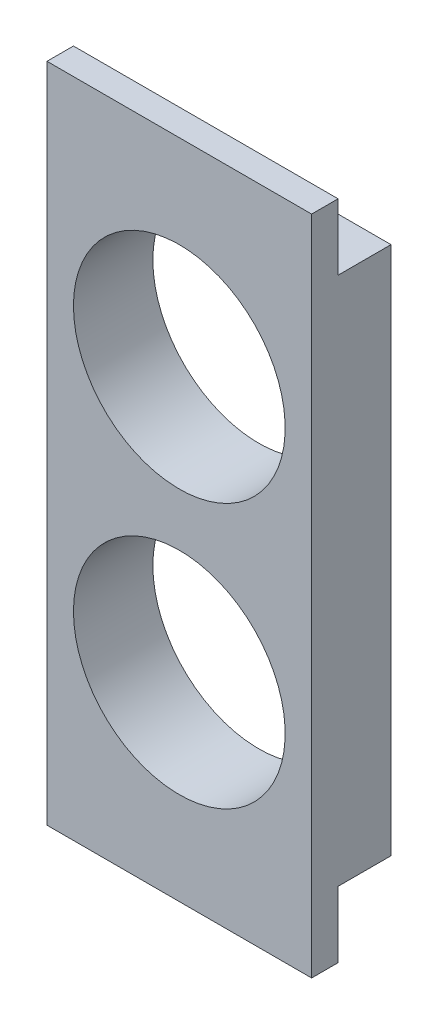
SolidWorks part; units mm, degrees
ref_plane "前视基准面" through (0, 0, 0) normal (0, 0, 1) x (1, 0, 0)
ref_plane "上视基准面" through (0, 0, 0) normal (0, 1, 0) x (1, 0, 0)
ref_plane "右视基准面" through (0, 0, 0) normal (1, 0, 0) x (0, 0, -1)
sketch "草图1" plane through (0, 0, 0) normal (0, 0, 1) x (1, 0, 0)
  line L0 (0, 100) -> (0, -100) construction
  line L1 (50, -100) -> (-50, -100)
  line L2 (50, -100) -> (50, 100)
  line L3 (50, 100) -> (-50, 100)
  line L4 (-50, -100) -> (-50, 100)
  line L5 (50, -100) -> (-50, 100) construction
  line L6 (50, 100) -> (-50, -100) construction
  line L7 (-50, 0) -> (50, 0) construction
  circle A0 centre (0, 50) radius 40
  circle A1 centre (0, -50) radius 40
  point P0 (0, 0)
  dimension "D3" = 80
  dimension "D1" = 100
  dimension "D2" = 200
  dimension "D4" = 50
extrude "凸台-拉伸1" add sketch "草图1" along normal blind 20
sketch "草图2" plane through (0, 0, 20) normal (0, 0, 1) x (1, 0, 0)
  line L0 (-50, 100) -> (-50, -100) construction
  line L1 (50, -125) -> (-50, -125)
  line L2 (50, -125) -> (50, 125)
  line L3 (50, 125) -> (-50, 125)
  line L4 (-50, -125) -> (-50, 125)
  line L5 (50, -125) -> (-50, 125) construction
  line L6 (50, 125) -> (-50, -125) construction
  point P0 (0, 0)
  dimension "D1" = 250
extrude "凸台-拉伸2" add sketch "草图2" along normal blind 10
sketch "草图3" plane through (0, 0, 20) normal (0, 0, -1) x (-1, 0, 0)
  circle A1 centre (0, 50) radius 40
  circle A2 centre (0, 50) radius 40
  circle A3 centre (0, -50) radius 40
  circle A4 centre (0, -50) radius 40
  dimension "D1" = 0
  dimension "D2" = 0
extrude "切除-拉伸1" cut sketch "草图3" against normal through all
sketch "草图4" plane through (0, 100, 0) normal (0, 1, 0) x (1, 0, 0)
  line L0 (50, 0) -> (50, -20) construction
  line L1 (50, -10) -> (25.1207, -10) construction
  line L2 (-50, -20) -> (-50, 0) construction
  circle A0 centre (-40, -10) radius 5
  dimension "D1" = 10
  dimension "D2" = 10
extrude "切除-拉伸2" cut sketch "草图4" against normal blind 20
